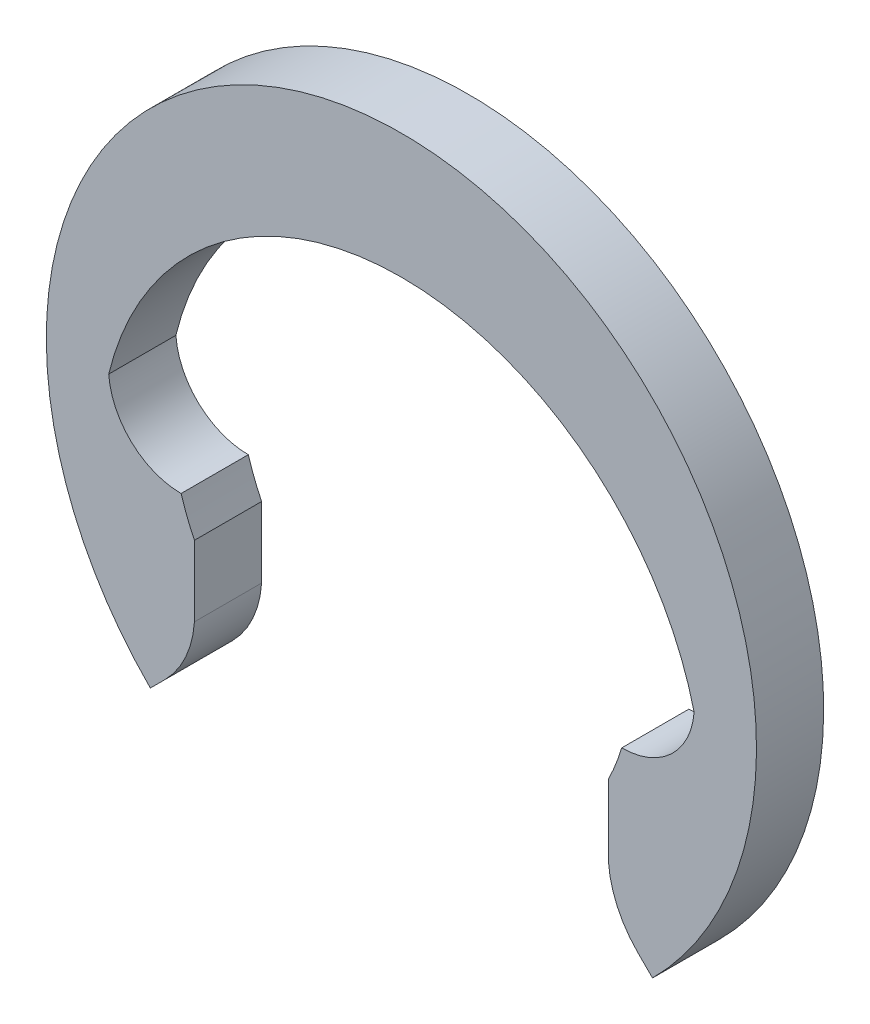
SolidWorks part; units mm, degrees
material "AISI 1035 Steel (SS)"
ref_plane "Front" through (0, 0, 0) normal (0, 0, 1) x (1, 0, 0)
ref_plane "Top" through (0, 0, 0) normal (0, 1, 0) x (1, 0, 0)
ref_plane "Right" through (0, 0, 0) normal (1, 0, 0) x (0, 0, -1)
sketch "Layout" plane through (0, 0, 0) normal (0, 0, 1) x (1, 0, 0)
  line L0 (0, 3.7) -> (0, -3.7) construction
  line L1 (-2.4, 0) -> (-3.7, 0) construction
  line L2 (-3.7, 0) -> (-4.4, 0) construction
  line L3 (-2.4, 0) -> (2.4, 0) construction
  line L4 (-2.1567, -2.1567) -> (-2.1567, -1.053) construction
  line L5 (-2.2956, -0.7) -> (2.2956, -0.7) construction
  line L6 (-2.4, 0) -> (-2.4, -0.7) construction
  line L7 (0, 0) -> (-1.6971, -1.6971) construction
  line L8 (-1.6971, -1.6971) -> (-2.6163, -2.6163) construction
  circle A0 centre (0, 0) radius 3.7 construction
  circle A1 centre (0, 0) radius 2.4 construction
  arc A2 (0, 2.4) -> (-3.05, 0) centre (0, -0.738) ccw construction
  circle A3 centre (0, 0) radius 3.8 construction
  arc A4 (-3.05, 0) -> (-2.2956, -0.7) centre (-2.2956, 0.0565) ccw construction
  dimension "D1" = 45
sketch "Sketch2" plane through (0, 0, 0) normal (0, 0, 1) x (1, 0, 0)
  line L0 (-2.1567, -2.1567) -> (-2.1567, -1.7888) construction
  line L1 (-2.1567, -1.7888) -> (-2.1567, -1.4209)
  line L2 (-2.1567, -1.4209) -> (-2.1567, -1.053)
  line L4 (0, 3.7) -> (0, -3.7) construction
  line L5 (-2.1567, -2.1567) -> (-2.3099, -2.3099) construction
  line L6 (0, 3.7) -> (0, 2.4) construction
  line L7 (-2.3099, -2.3099) -> (-2.4631, -2.4631) construction
  line L8 (-2.4631, -2.4631) -> (-2.6163, -2.6163)
  line L9 (-1.6971, -1.6971) -> (-2.6163, -2.6163) construction
  line L10 (2.1567, -1.4209) -> (2.1567, -1.053)
  line L11 (2.1567, -1.7888) -> (2.1567, -1.4209)
  line L12 (2.4631, -2.4631) -> (2.6163, -2.6163)
  circle A0 centre (0, 0) radius 3.7 construction
  arc A1 (0, 2.4) -> (-3.05, 0) centre (0, -0.738) ccw construction
  arc A2 (-3.05, 0) -> (-2.2956, -0.7) centre (-2.2956, 0.0565) ccw construction
  circle A3 centre (0, 0) radius 2.4 construction
  arc A4 (2.6163, -2.6163) -> (-2.6163, -2.6163) centre (0, 0) ccw
  arc A5 (3.05, 0) -> (-3.05, 0) centre (0, -0.738) ccw
  arc A6 (-3.05, 0) -> (-2.2956, -0.7) centre (-2.2956, 0.0565) ccw
  arc A7 (-2.2956, -0.7) -> (-2.1567, -1.053) centre (0, 0) ccw
  arc A8 (-2.1567, -1.7888) -> (-2.4631, -2.4631) centre (-3.2087, -1.7175) cw
  arc A9 (2.1567, -1.7888) -> (2.4631, -2.4631) centre (3.2087, -1.7175) ccw
  arc A10 (2.2956, -0.7) -> (2.1567, -1.053) centre (0, 0) cw
  arc A11 (3.05, 0) -> (2.2956, -0.7) centre (2.2956, 0.0565) cw
extrude "Boss-Extrude1" add sketch "Sketch2" along normal blind 0.7
ref_axis "Center Axis 1" through (0, 0, 0.7) along (0, 0, -1)
ref_plane "Contact Plane 1" through (0, 0, 0.7) normal (0, 0, 1) x (1, 0, 0)
ref_plane "Contact Plane 2" through (0, 0, 0) normal (0, 0, -1) x (-1, 0, 0)
equation "\"D1@Boss-Extrude1\"=\"thickness@Layout\""
